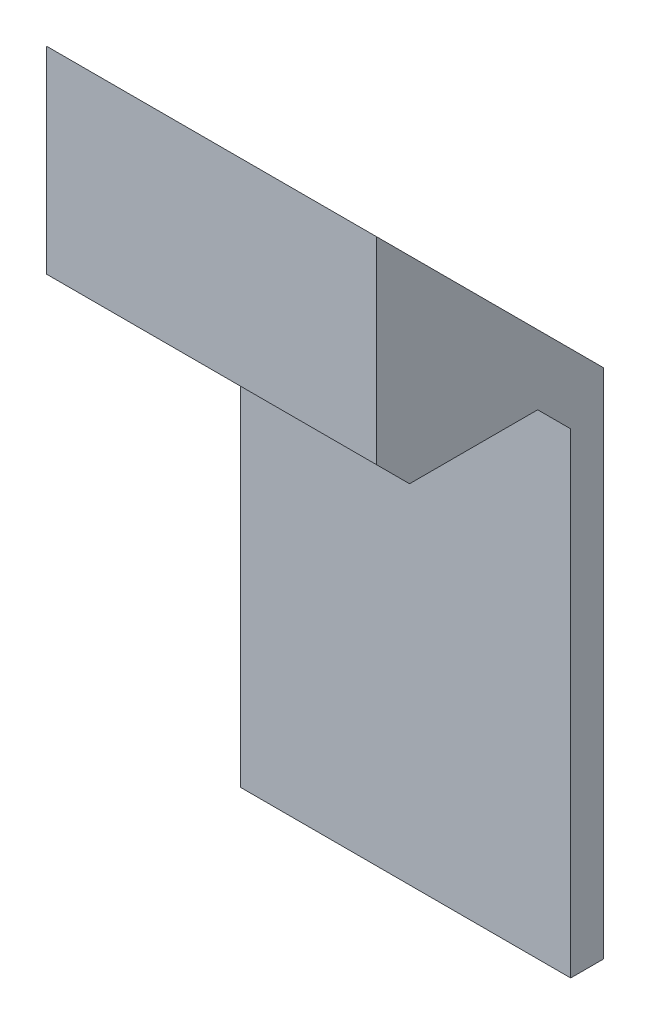
SolidWorks part; units mm, degrees
ref_plane "Front Plane" through (0, 0, 0) normal (0, 0, 1) x (1, 0, 0)
ref_plane "Top Plane" through (0, 0, 0) normal (0, 1, 0) x (1, 0, 0)
ref_plane "Right Plane" through (0, 0, 0) normal (1, 0, 0) x (0, 0, -1)
sketch "Sketch1" plane through (0, 0, 0) normal (1, 0, 0) x (0, 0, -1)
  line L1 (0.4679, 7.2521) -> (-0.4114, 7.2521)
  line L2 (0.4679, 7.2521) -> (0.4679, -8.2479)
  line L3 (0.4679, -8.2479) -> (-0.5321, -8.2479)
  line L4 (-0.5321, 7.1521) -> (-0.5321, -8.2479)
  line L5 (0.4679, 7.2521) -> (-0.5321, -8.2479) construction
  line L6 (0.4679, -8.2479) -> (-0.4114, 7.2521) construction
  line L7 (-0.4114, 7.2521) -> (-6.4114, 7.2521)
  line L9 (-0.5321, 7.1521) -> (-6.4114, 7.1521)
  line L10 (-6.4114, 7.2521) -> (-6.4114, 7.1521)
  point P0 (0, 0)
  dimension "D1" = 15.5
  dimension "D2" = 1
  dimension "D3" = 0.1
  dimension "D4" = 6
extrude "Boss-Extrude1" add sketch "Sketch1" along normal blind 10
sketch "Sketch3" plane through (0, 7.2521, 0) normal (0, 1, 0) x (1, 0, 0)
  line L4 (0, 0.4679) -> (0, -6.4114)
  line L5 (0, -6.4114) -> (10, -6.4114)
  line L6 (10, -6.4114) -> (10, 0.4679)
  line L7 (10, 0.4679) -> (0, 0.4679)
  line L8 (0, 0.4679) -> (0, -6.4114)
  line L9 (0, -6.4114) -> (10, -6.4114)
  line L10 (10, -6.4114) -> (10, 0.4679)
  line L11 (10, 0.4679) -> (0, 0.4679)
  dimension "D1" = 0
extrude "Boss-Extrude2" add sketch "Sketch3" along normal blind 7
chamfer "Chamfer1" distance 7 angle 45 1 edges at (5, 14.2521, -0.4679)
sketch "Sketch2" plane through (0, 7.1521, 0) normal (0, 1, 0) x (1, 0, 0)
  line L0 (4.9892, -6.1998) -> (5, -0.5321) construction
  line L3 (10, -0.5321) -> (0, -0.5321) construction
  line L4 (10, -6.4114) -> (0, -6.4114) construction
  circle A0 centre (4.9945, -3.4114) radius 1.25
  dimension "D1" = 2.5
  dimension "D2" = 3
extrude "Cut-Extrude1" cut sketch "Sketch2" along normal up to surface (5.2293 mm away) up to face at (5, 10.6918, 2.9718)
chamfer "Chamfer2" distance 1 angle 45 2 edges at (5, 7.1521, 6.4114) (5, 7.1521, 0.5321)
